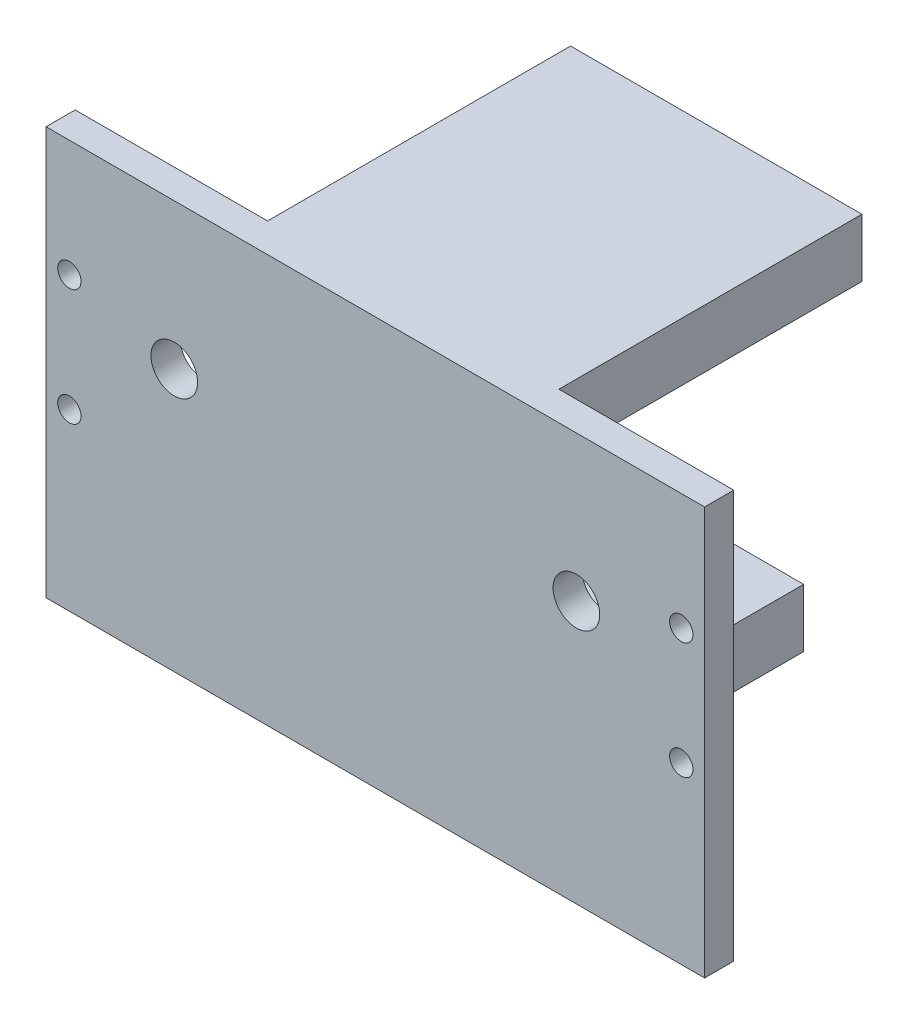
SolidWorks part; units mm, degrees
ref_plane "前视基准面" through (0, 0, 0) normal (0, 0, 1) x (1, 0, 0)
ref_plane "上视基准面" through (0, 0, 0) normal (0, 1, 0) x (1, 0, 0)
ref_plane "右视基准面" through (0, 0, 0) normal (1, 0, 0) x (0, 0, -1)
sketch "草图1" plane through (0, 0, 0) normal (0, 0, 1) x (1, 0, 0)
  line L1 (-56.5, 35) -> (56.5, 35)
  line L2 (-56.5, 35) -> (-56.5, -35)
  line L3 (-56.5, -35) -> (56.5, -35)
  line L4 (56.5, 35) -> (56.5, -35)
  line L5 (-56.5, 35) -> (56.5, -35) construction
  line L6 (-56.5, -35) -> (56.5, 35) construction
  point P0 (0, 0)
  dimension "D1" = 113
  dimension "D2" = 70
extrude "凸台-拉伸1" add sketch "草图1" along normal blind 5 contours L1 L4 L3 L2
sketch "草图2" plane through (0, 0, 0) normal (0, 0, -1) x (-1, 0, 0)
  line L0 (56.5, -35) -> (-56.5, -35) construction
  line L1 (-56.5, 35) -> (-56.5, -35) construction
  line L2 (56.5, 35) -> (-56.5, 35) construction
  line L3 (-16.5, -35) -> (13.5, -35)
  line L4 (-16.5, -35) -> (-16.5, -25)
  line L5 (-16.5, -25) -> (13.5, -25)
  line L6 (13.5, -35) -> (13.5, -25)
  line L7 (-26.5, 35) -> (23.5, 35)
  line L8 (-26.5, 35) -> (-26.5, 25)
  line L9 (-26.5, 25) -> (23.5, 25)
  line L10 (23.5, 35) -> (23.5, 25)
  point P0 (-16.5, -35)
  dimension "D1" = 40
  dimension "D2" = 30
  dimension "D3" = 10
  dimension "D4" = 30
  dimension "D5" = 50
  dimension "D6" = 10
extrude "凸台-拉伸2" add sketch "草图2" along normal blind 52
sketch "草图3" plane through (0, 0, 0) normal (0, 0, -1) x (-1, 0, 0)
  line L0 (-26.5, 35) -> (-56.5, 35) construction
  line L2 (-56.5, 35) -> (-56.5, -35) construction
  line L3 (56.5, 35) -> (23.5, 35) construction
  line L4 (56.5, 35) -> (56.5, -35) construction
  circle A0 centre (-34.5, 10) radius 4
  circle A1 centre (34.5, 10) radius 4
  point P0 (-34.5, 10)
  point P9 (40, 35)
  dimension "D3" = 25
  dimension "D1" = 25
  dimension "D2" = 22
  dimension "D4" = 22
extrude "切除-拉伸1" cut sketch "草图3" against normal through all
sketch "草图5" plane through (0, 0, 5) normal (0, 0, 1) x (1, 0, 0)
  line L0 (-56.5, 35) -> (56.5, 35) construction
  line L1 (-56.5, 35) -> (-56.5, -35) construction
  circle A0 centre (-52.5, 15) radius 2
  circle A1 centre (52.5, 15) radius 2
  circle A2 centre (52.5, -5) radius 2
  circle A3 centre (-52.5, -5) radius 2
  point P0 (-52.5, 15)
  dimension "D1" = 20
  dimension "D2" = 4
  dimension "D5" = 105
  dimension "D3" = 2
  dimension "D4" = 2
extrude "切除-拉伸2" cut sketch "草图5" against normal through all
